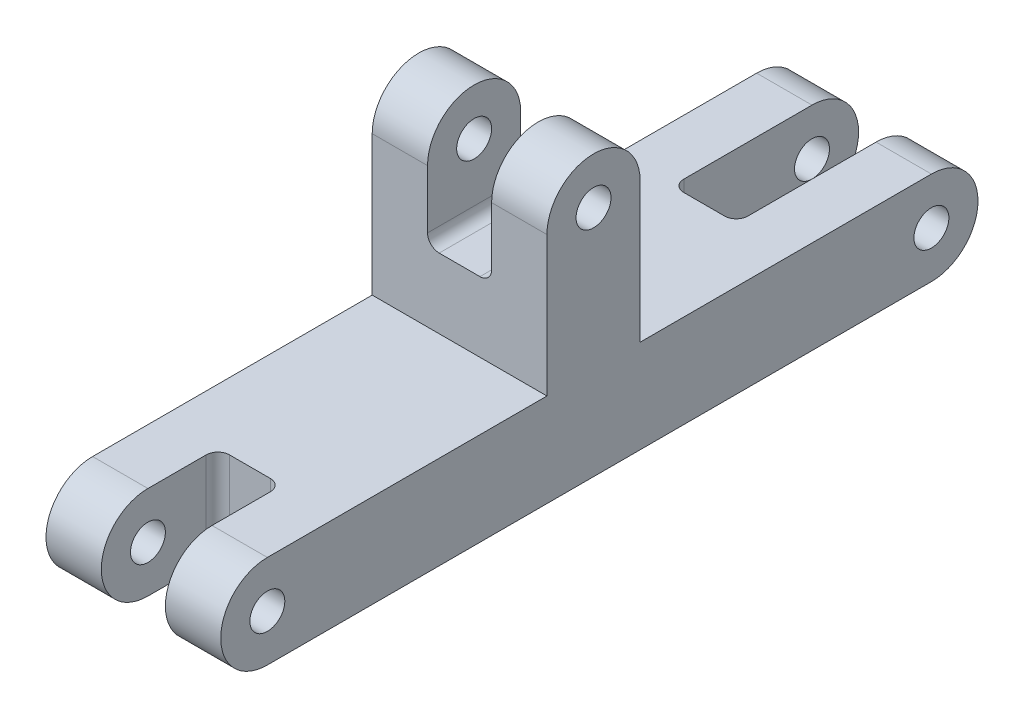
SolidWorks part; units mm, degrees
ref_plane "Alzado" through (0, 0, 0) normal (0, 0, 1) x (1, 0, 0)
ref_plane "Planta" through (0, 0, 0) normal (0, 1, 0) x (1, 0, 0)
ref_plane "Vista lateral" through (0, 0, 0) normal (1, 0, 0) x (0, 0, -1)
sketch "Croquis1" plane through (0, 0, 0) normal (1, 0, 0) x (0, 0, -1)
  line L0 (-12.5, 0) -> (12.5, 0) construction
  line L1 (-12.5, 4) -> (-20.5, 4) construction
  line L2 (-12.5, -4) -> (12.5, -4)
  line L3 (-12.5, 4) -> (12.5, 4)
  line L5 (-20.5, 4) -> (-20.5, 16)
  line L6 (-20.5, 16) -> (-12.5, 16) construction
  line L7 (-12.5, 4) -> (-12.5, 16)
  line L8 (-20.5, 4) -> (-44.5, 4)
  line L9 (-12.5, -4) -> (-44.5, -4)
  line L10 (-44.5, 4) -> (-44.5, -4) construction
  arc A0 (-12.5, 4) -> (-12.5, -4) centre (-12.5, 0) ccw construction
  arc A1 (12.5, -4) -> (12.5, 4) centre (12.5, 0) ccw
  circle A2 centre (12.5, 0) radius 1.5
  arc A3 (-12.5, 16) -> (-20.5, 16) centre (-16.5, 16) ccw
  circle A4 centre (-16.5, 16) radius 1.5
  circle A5 centre (-12.5, 0) radius 1.5 construction
  arc A6 (-44.5, 4) -> (-44.5, -4) centre (-44.5, 0) ccw
  circle A7 centre (-44.5, 0) radius 1.5
  point P3 (0, 0)
  dimension "D2" = 4
  dimension "D3" = 3
  dimension "D4" = 4
  dimension "D7" = 24
  dimension "D1" = 25
  dimension "D6" = 12
extrude "Saliente-Extruir1" add sketch "Croquis1" along normal mid plane 15
sketch "Croquis2" plane through (0, 0, 0) normal (1, 0, 0) x (0, 0, -1)
  line L0 (-20.5, 16) -> (-20.5, 4) construction
  line L1 (-20.5, 10) -> (-12.5, 10)
  line L2 (-20.5, 10) -> (-20.5, 20)
  line L3 (-20.5, 20) -> (-12.5, 20)
  line L4 (-12.5, 10) -> (-12.5, 20)
  line L5 (-12.5, 4) -> (-12.5, 16) construction
  line L11 (-44.5, -4) -> (12.5, -4) construction
  line L12 (12.5, 4) -> (-12.5, 4) construction
  line L13 (0.5, 4) -> (16.5, 4)
  line L14 (0.5, 4) -> (0.5, -4)
  line L15 (0.5, -4) -> (16.5, -4)
  line L16 (16.5, 4) -> (16.5, -4)
  line L18 (-38.5, 4) -> (-48.5, 4)
  line L19 (-38.5, 4) -> (-38.5, -4)
  line L20 (-38.5, -4) -> (-48.5, -4)
  line L21 (-48.5, 4) -> (-48.5, -4)
  line L22 (-44.5, -4) -> (12.5, -4) construction
  line L23 (-20.5, 4) -> (-44.5, 4) construction
  arc A0 (-12.5, 16) -> (-20.5, 16) centre (-16.5, 16) ccw construction
  arc A2 (12.5, -4) -> (12.5, 4) centre (12.5, 0) ccw construction
  arc A5 (-44.5, 4) -> (-44.5, -4) centre (-44.5, 0) ccw construction
  dimension "D5" = 10
  dimension "D1" = 10
  dimension "D3" = 16
extrude "Cortar-Extruir1" cut sketch "Croquis2" against normal mid plane 5.5
fillet "Redondeo1" radius 1 6 edges at (2.75, 0, 38.5) (-2.75, 0, 38.5) (2.75, 0, -0.5) (-2.75, 0, -0.5) (2.75, 10, 16.5) (-2.75, 10, 16.5)
